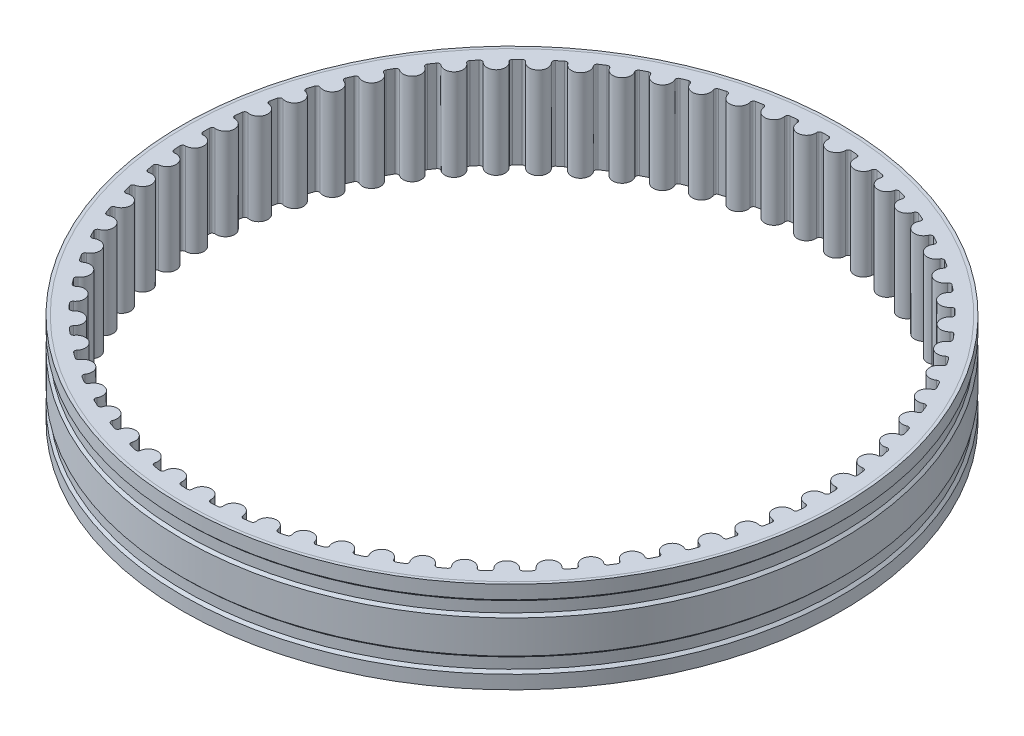
SolidWorks part; units mm, degrees
ref_plane "Front Plane" through (0, 0, 0) normal (0, 0, 1) x (1, 0, 0)
ref_plane "Top Plane" through (0, 0, 0) normal (0, 1, 0) x (1, 0, 0)
ref_plane "Right Plane" through (0, 0, 0) normal (1, 0, 0) x (0, 0, -1)
sketch "Sketch2" plane through (0, 0, 0) normal (1, 0, 0) x (0, 0, -1)
  line L0 (49.3254, 7.5) -> (49.3254, -7.5)
  line L1 (49.3254, -7.5) -> (53.1254, -7.5)
  line L2 (53.1254, -7.5) -> (53.1254, 7.5)
  line L3 (53.1254, 7.5) -> (49.3254, 7.5)
  line L4 (0, 0) -> (53.1254, 0) construction
  line L5 (53.1254, -5.08) -> (53.5454, -5.5)
  line L6 (0, 0) -> (0, 23.3027) construction
  line L7 (53.1254, 2.92) -> (53.5454, 2.5)
  line L8 (53.5454, 2.5) -> (53.5454, -2.5)
  line L9 (53.1254, 7.5) -> (54.0454, 7.5)
  line L10 (54.0454, 7.5) -> (54.0454, -7.5)
  line L11 (54.0454, -7.5) -> (53.1254, -7.5)
  line L12 (53.1254, -2.92) -> (53.5454, -2.5)
  line L13 (53.1254, 5.08) -> (53.5454, 5.5)
  line L14 (53.5454, 5.5) -> (53.5454, 7.5)
  line L15 (53.5454, -5.5) -> (53.5454, -7.5)
  line L16 (51.7254, -7.5) -> (51.7254, 7.5) construction
  line L17 (54.0454, 5.2929) -> (53.6254, 4.8729)
  line L18 (53.6254, 4.8729) -> (53.6254, 3.1271)
  line L19 (53.6254, 3.1271) -> (54.0454, 2.7071)
  line L20 (53.6254, -3.1271) -> (54.0454, -2.7071)
  line L21 (54.0454, -5.2929) -> (53.6254, -4.8729)
  line L22 (53.6254, -4.8729) -> (53.6254, -3.1271)
  point P15 (53.5454, 0)
  dimension "D1" = 15
  dimension "D2" = 51.7254
  dimension "D3" = 3.8
  dimension "D4" = 135
  dimension "D5" = 5
  dimension "D6" = 0.42
  dimension "D7" = 0.5
  dimension "D8" = 45
  dimension "D9" = 1.4
  dimension "D10" = 2
  dimension "D11" = 0.5
  dimension "D12" = 0.5
  dimension "D13" = 0.5
revolve "Revolve1" add sketch "Sketch2" angle 360 about L6 region at (0, 0, -51.2254) region at (0, 6.3917, -53.3287) region at (0, -6.3917, -53.3287) region at (0, 0, -53.3299)
revolve "Revolve2" add sketch "Sketch2<3>" angle 360 about L6 region at (0, 0, -53.6591)
sketch "Sketch2<3>" plane through (0, 0, 0) normal (1, 0, 0) x (0, 0, -1) same geometry as "Sketch2"
sketch "Sketch3" plane through (0, 0, 0) normal (0, 1, 0) x (1, 0, 0)
  line L0 (0, -52.2554) -> (0, 0) construction
  line L1 (0, -52.2554) -> (0, -51.3854) construction
  line L2 (2.5, -51.3245) -> (2.5, -49.262)
  line L3 (-2.5, -51.3245) -> (-2.5, -49.262)
  arc A0 (1.4983, -50.8983) -> (1.944, -51.3486) centre (1.9278, -50.9189) ccw
  arc A2 (1.4983, -50.8983) -> (-1.4983, -50.8983) centre (0, -50.8264) ccw
  circle A4 centre (0, 0) radius 53.1254 construction
  circle A5 centre (0, 0) radius 53.1254 construction
  circle A6 centre (0, 0) radius 49.3254 construction
  circle A7 centre (0, 0) radius 49.3254
  arc A8 (1.944, -51.3486) -> (-1.944, -51.3486) centre (0, 0) cw
  arc A9 (-1.4983, -50.8983) -> (-1.944, -51.3486) centre (-1.9278, -50.9189) cw
  arc A10 (-1.944, -51.3486) -> (-2.5, -51.3245) centre (0, 0) cw
  arc A11 (1.944, -51.3486) -> (2.5, -51.3245) centre (0, 0) ccw
  dimension "D1" = 0.87
  dimension "D2" = 1.5
  dimension "D3" = 2.06
  dimension "D4" = 0.43
  dimension "D6" = 0.001
  dimension "D5" = 5
extrude "Cut-Extrude1" cut sketch "Sketch3" against normal through all both and the other way through all contours A0 A11 L2 A7 L3 A10 A9 A2 region at (2.2197, 0, 51.2832)
pattern_circular "CirPattern1" count 65 over 360 about axis through (0, 0, 0) along (0, 1, 0) of "Cut-Extrude1" reverse direction yes
